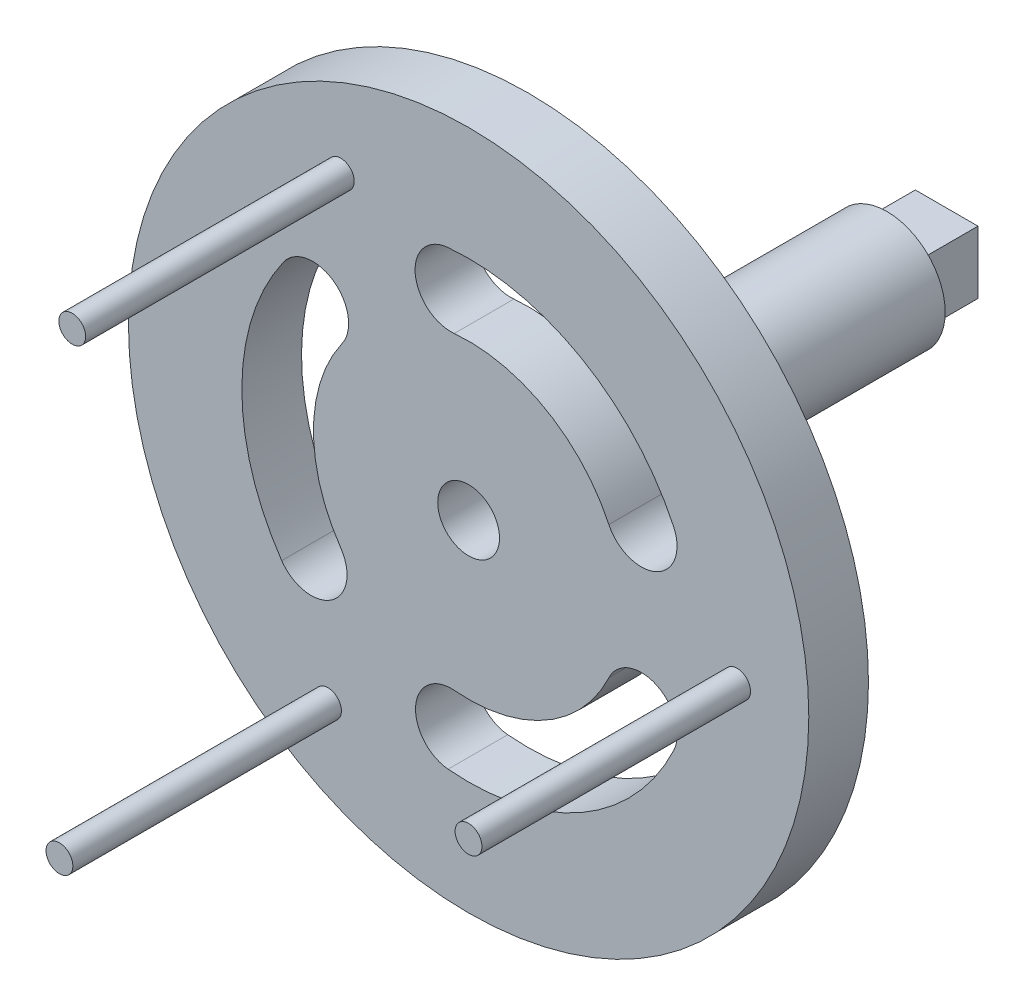
SolidWorks part; units mm, degrees
ref_plane "Front Plane" through (0, 0, 0) normal (1, 0, 0) x (0, 1, 0)
ref_plane "Top Plane" through (0, 0, 0) normal (0, 0, 1) x (0, 1, 0)
ref_plane "Right Plane" through (0, 0, 0) normal (0, 1, 0) x (-1, 0, 0)
sketch "Sketch1" plane through (0, 0, 0) normal (0, 0, 1) x (0, 1, 0)
  circle A0 centre (0, 0) radius 57
  circle A1 centre (0, 0) radius 5.175
  dimension "D1" = 114
  dimension "D2" = 10.35
extrude "Boss-Extrude1" add sketch "Sketch1" along normal blind 10
sketch "Sketch3" plane through (0, 0, 10) normal (0, 0, 1) x (1, 0, 0)
  circle A5 centre (-21.4189, 39.5757) radius 2.25
  dimension "D1" = 4.5
extrude "Boss-Extrude2" add sketch "Sketch3" along normal blind 45 contours A5 region at (-21.4189, 39.5757, 10)
sketch "Sketch4" plane through (0, 0, 0) normal (0, 0, -1) x (-1, 0, 0)
  circle A0 centre (0, 0) radius 9.75
  circle M2 centre (0, 0) radius 5.175
  dimension "D1" = 19.5
extrude "Boss-Extrude3" add sketch "Sketch4" along normal blind 60.1 contours A0 M2 region at (9.4742, 0, 0)
sketch "Sketch5" plane through (0, 0, -60.1) normal (0, 0, -1) x (-1, 0, 0)
  line L1 (5.25, 5.25) -> (-5.25, 5.25)
  line L2 (5.25, 5.25) -> (5.25, -5.25)
  line L3 (5.25, -5.25) -> (-5.25, -5.25)
  line L4 (-5.25, 5.25) -> (-5.25, -5.25)
  line L5 (5.25, 5.25) -> (-5.25, -5.25) construction
  line L6 (5.25, -5.25) -> (-5.25, 5.25) construction
  point P0 (0, 0)
  dimension "D1" = 10.5
  dimension "D2" = 10.5
extrude "Boss-Extrude4" add sketch "Sketch5" along normal blind 10
sketch "Sketch6" plane through (0, 0, 0) normal (0, 0, -1) x (-1, 0, 0)
  arc A0 (2.898, -31.8685) -> (-28.9554, -13.6229) centre (0, 0) cw construction
  arc A1 (-34.3845, -16.1772) -> (3.4414, -37.8438) centre (0, 0) ccw
  arc A2 (-23.5263, -11.0686) -> (2.3547, -25.8932) centre (0, 0) ccw
  arc A3 (-23.5263, -11.0686) -> (-34.3845, -16.1772) centre (-28.9554, -13.6229) ccw
  arc A4 (3.4414, -37.8438) -> (2.3547, -25.8932) centre (2.898, -31.8685) ccw
  arc A10 (-28.9227, 13.6921) -> (2.9743, 31.8615) centre (0, 0) cw construction
  arc A11 (3.5319, 37.8355) -> (-34.3458, 16.2594) centre (0, 0) ccw
  arc A12 (2.4166, 25.8875) -> (-23.4997, 11.1249) centre (0, 0) ccw
  arc A13 (2.4166, 25.8875) -> (3.5319, 37.8355) centre (2.9743, 31.8615) ccw
  arc A14 (-34.3458, 16.2594) -> (-23.4997, 11.1249) centre (-28.9227, 13.6921) ccw
  arc A20 (26.1096, 18.501) -> (26.3758, -18.1195) centre (0, 0) cw construction
  arc A21 (31.3213, -21.5169) -> (31.0052, 21.9699) centre (0, 0) ccw
  arc A22 (21.4303, -14.7221) -> (21.2141, 15.0321) centre (0, 0) ccw
  arc A23 (21.4303, -14.7221) -> (31.3213, -21.5169) centre (26.3758, -18.1195) ccw
  arc A24 (31.0052, 21.9699) -> (21.2141, 15.0321) centre (26.1096, 18.501) ccw
  point P4 (-15.9051, -27.7674)
  point P17 (-15.8386, 27.8054)
  point P34 (31.9992, 0.2326)
extrude "Cut-Extrude1" cut sketch "Sketch6" against normal blind 10 contours A21 A24 A22 A23 | A1 A4 A2 A3 | A11 A14 A12 A13 region at (14.5641, -25.4262, 0) region at (14.5032, 25.461, 0) region at (-29.3139, 0.2131, 0)
pattern_circular "CirPattern1" count 3 over 360 about axis through (0, 0, -60.1) along (0, 0, 1) of "Boss-Extrude2"
